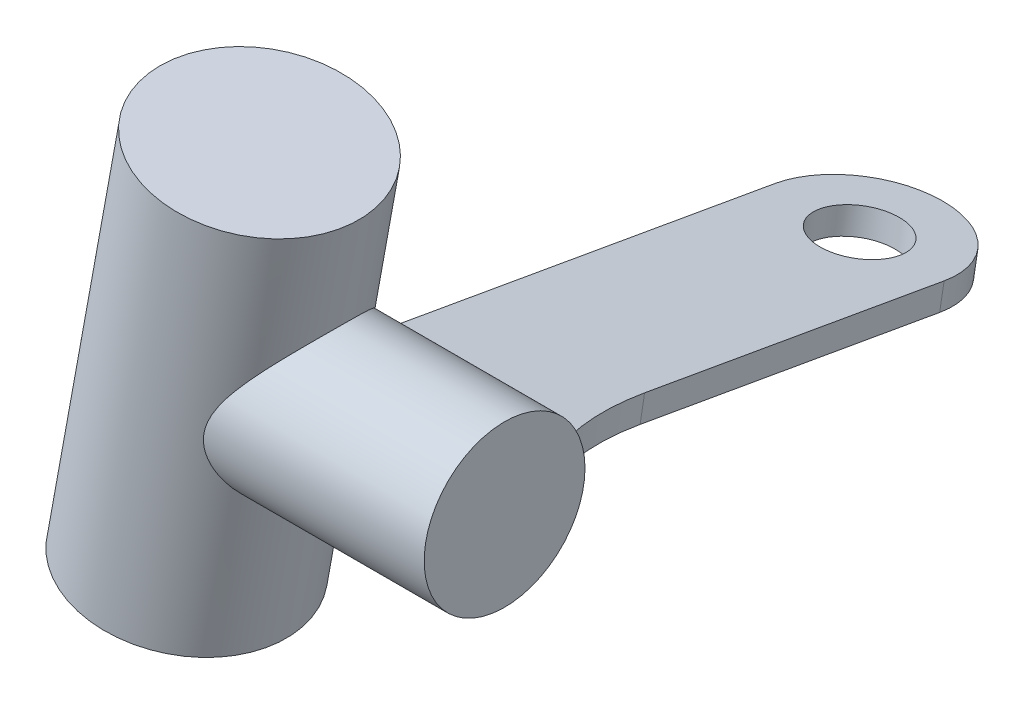
SolidWorks part; units mm, degrees
ref_plane "Front Plane" through (0, 0, 0) normal (0, 0, 1) x (1, 0, 0)
ref_plane "Top Plane" through (0, 0, 0) normal (0, 1, 0) x (1, 0, 0)
ref_plane "Right Plane" through (0, 0, 0) normal (1, 0, 0) x (0, 0, -1)
sketch "Sketch1" plane through (0, 0, 0) normal (1, 0, 0) x (0, 0, -1)
  circle A0 centre (0, 0) radius 10
  dimension "D1" = 20
extrude "Boss-Extrude1" add sketch "Sketch1" along normal blind 25 and the other way blind 10
ref_point "Point1"
ref_plane "Plane1" through (-10, 0, 0) normal (0.1736, 0.9848, -0.0071) x (0.9848, -0.1737, 0)
sketch "Sketch2" plane through (-10, 0, 0) normal (0.1736, 0.9848, -0.0071) x (0.9848, -0.1737, 0)
  circle A0 centre (0, 0) radius 12.5
  dimension "D1" = 25
extrude "Boss-Extrude2" add sketch "Sketch2" along normal mid plane 50
ref_plane "Plane2" through (-9.6985, 1.7101, -0.0123) normal (-0.9848, 0.1736, -0.0013) x (0.1736, 0.9848, -0.0071)
sketch "Sketch5" plane through (0, 0, 0) normal (1, 0, 0) x (0, 0, -1)
  line L0 (0.7938, 1.3748) -> (-0.7937, -1.3748)
  line L1 (-0.7937, -1.3748) -> (23.8645, -15.6113)
  line L2 (23.8645, -15.6113) -> (25.452, -12.8616)
  line L3 (25.452, -12.8616) -> (0.7938, 1.3748)
  line L4 (0, 0) -> (50.9555, 0) construction
  line L5 (12.3221, -24.7097) -> (12.6773, 24.5294) construction
  point P8 (12.4616, -5.3616)
  point P10 (0, 0)
  point P11 (0, 0)
  dimension "D1" = 3.175
  dimension "D2" = 30
  dimension "D3" = 15
extrude "Boss-Extrude3" add sketch "Sketch5" along normal blind 15 and the other way blind 15
sketch "Sketch6" plane through (0, 1.3748, -0.7938) normal (0, 0.866, -0.5) x (1, 0, 0)
  line L0 (15, 28.4729) -> (15, 10)
  line L1 (15, 28.4729) -> (15, 9.8732) construction
  line L2 (15, 10) -> (8.2764, 28.4729)
  line L3 (-15, 28.4729) -> (15, 28.4729) construction
  line L4 (8.2764, 28.4729) -> (15, 28.4729)
  dimension "D1" = 20
extrude "Cut-Extrude1" cut sketch "Sketch6" against normal blind 15
ref_plane "Plane3" through (0, -11.0595, 1.9501) normal (0, 0.9848, -0.1736) x (1, 0, 0)
sketch "Sketch8" plane through (0, -11.0595, 1.9501) normal (0, 0.9848, -0.1736) x (1, 0, 0)
  line L0 (8.2764, 26.2128) -> (-15, 26.2128)
  line L1 (-15, 26.2128) -> (-15, 76.2128)
  line L2 (-15, 76.2128) -> (6, 76.2128)
  line L3 (6, 76.2128) -> (6, 38.3927)
  line L4 (15, 8.854) -> (8.2764, 26.2128) construction
  circle A0 centre (-4.5, 76.2128) radius 10.5
  arc A1 (8.2764, 26.2128) -> (6, 38.3927) centre (39.7221, 38.3927) cw
  dimension "D1" = 21
  dimension "D2" = 50
extrude "Boss-Extrude4" add sketch "Sketch8" along normal blind 3.175 contours L0 A1 L3 A0 L1 | L2 A0 | L2 A0 region at (-4.385, -19.2159, -44.3073) region at (-4.5, -25.0675, -77.4935) region at (-4.5, -23.5199, -68.7163)
sketch "Sketch9" plane through (0, -7.9327, 1.3987) normal (0, 0.9848, -0.1736) x (1, 0, 0)
  line L1 (10.9695, 56.0127) -> (13.8263, 16.7921)
  arc A0 (13.8263, 16.7921) -> (10.9695, 56.0127) centre (39.7221, 38.3927) cw
  arc A1 (6, 38.3927) -> (8.0653, 26.7727) centre (39.7221, 38.3927) ccw construction
extrude "Cut-Extrude2" cut sketch "Sketch9" against normal through all both and the other way through all
sketch "Sketch10" plane through (0, -7.9327, 1.3987) normal (0, 0.9848, -0.1736) x (1, 0, 0)
  circle A0 centre (-4.5, 76.2128) radius 5
  arc A1 (6, 76.2128) -> (-15, 76.2128) centre (-4.5, 76.2128) ccw construction
  dimension "D1" = 10
extrude "Cut-Extrude3" cut sketch "Sketch10" against normal blind 10
sketch "Sketch11" plane through (0, -7.9327, 1.3987) normal (0, 0.9848, -0.1736) x (1, 0, 0)
  point P0 (-4.5, 76.2128)
